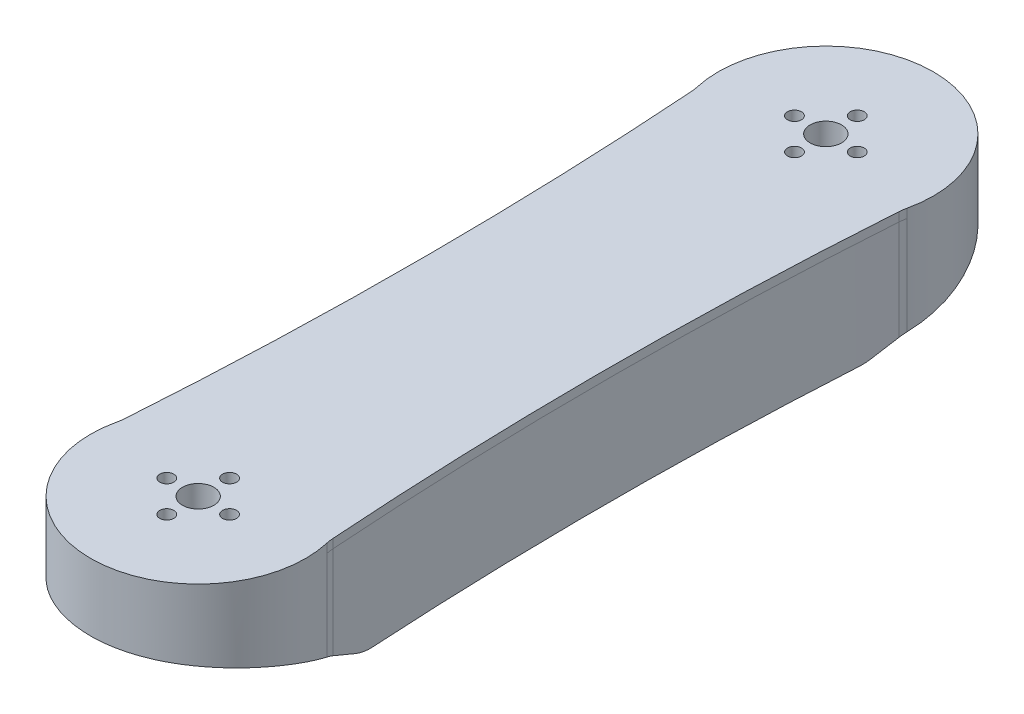
SolidWorks part; units mm, degrees
ref_plane "前视基准面" through (0, 0, 0) normal (0, 0, 1) x (1, 0, 0)
ref_plane "上视基准面" through (0, 0, 0) normal (0, 1, 0) x (1, 0, 0)
ref_plane "右视基准面" through (0, 0, 0) normal (1, 0, 0) x (0, 0, -1)
other "Configuration Table"
sketch "草图1" plane through (0, 0, 0) normal (0, 1, 0) x (1, 0, 0)
  line L0 (0, 140) -> (0, 0) construction
  line L1 (-23.2379, 6) -> (23.2379, 6) construction
  line L2 (-23.2379, 134) -> (23.2379, 134) construction
  circle A0 centre (0, 0) radius 24
  circle A1 centre (0, 140) radius 24
  spline S0 degree 2 poles (-23.2379, 134) (-18.7446, 70.0098) (-23.2379, 6) knots 0 0 0 1 1 1
  spline S1 degree 2 poles (23.2379, 134) (18.7446, 70.0098) (23.2379, 6) knots 0 0 0 1 1 1
  dimension "D1" = 48
  dimension "D2" = 140
  dimension "D3" = 6
  dimension "D4" = 6
  dimension "D5" = 60
  dimension "D6" = 42
extrude "凸台-拉伸1" add sketch "草图1" along normal blind 24 contours S1 A1 S0 A0 region at (0, 0, -69.9998)
extrude "凸台-拉伸2" add sketch "草图1<3>" along normal blind 26 contours A1 | A0 region at (0, 0, -140)
sketch "草图1<3>" plane through (0, 0, 0) normal (0, 1, 0) x (1, 0, 0) same geometry as "草图1"
sketch "草图2" plane through (0, 0, 0) normal (1, 0, 0) x (0, 0, -1)
  line L0 (-24, 0) -> (14, 0)
  line L1 (24, 0) -> (-24, 0) construction
  line L2 (164, 0) -> (116, 0) construction
  line L3 (164, 0) -> (164, 11)
  line L4 (164, 0) -> (164, 26) construction
  line L5 (-24, 0) -> (-24, 11)
  line L6 (-24, 26) -> (-24, 0) construction
  line L7 (126, 0) -> (164, 0)
  line L8 (70, -17.1118) -> (70, 61.7377) construction
  spline S0 degree 2 poles (-24, 11) (-3.7798, 9.1799) (14, 0) knots 0 0 0 1 1 1
  spline S1 degree 2 poles (164, 11) (145.3218, 4.4125) (126, 0) knots 0 0 0 1 1 1
  dimension "D1" = 11
  dimension "D2" = 38
  dimension "D3" = 11
  dimension "D4" = 38
extrude "切除-拉伸1" cut sketch "草图2" against normal through all both and the other way through all
ref_plane "基准面1" through (0, 20, 0) normal (0, 1, 0) x (1, 0, 0)
sketch "草图4" plane through (0, 20, 0) normal (0, 1, 0) x (1, 0, 0)
  arc A2 (-23.2379, 134) -> (23.2379, 134) centre (0, 140) ccw
  arc A3 (23.2379, 6) -> (-23.2379, 6) centre (0, 0) ccw
  arc A4 (-23.2379, 134) -> (23.2379, 134) centre (0, 140) ccw
  arc A5 (23.2379, 6) -> (-23.2379, 6) centre (0, 0) ccw
  parabola Q2 (23.2379, 6) -> (23.2379, 134) focus (476.7779, 71.0037) apex (20.9934, 72.0025)
  parabola Q3 (23.2379, 6) -> (23.2379, 134) focus (476.7779, 71.0037) apex (20.9934, 72.0025)
  parabola Q4 (-23.2379, 134) -> (-23.2379, 6) focus (-476.7779, 71.0037) apex (-20.9934, 72.0025)
  parabola Q5 (-23.2379, 134) -> (-23.2379, 6) focus (-476.7779, 71.0037) apex (-20.9934, 72.0025)
  dimension "D1" = 0
extrude "凸台-拉伸3" add sketch "草图4" along normal up to surface (6 mm away) up to face at (0, 26, -116)
sketch "草图6" plane through (0, 20, 0) normal (0, 1, 0) x (1, 0, 0)
  arc A2 (20.3332, 134.75) -> (-20.3332, 134.75) centre (0, 140) ccw
  circle A3 centre (0, 140) radius 21
  arc A5 (-20.3332, 5.25) -> (20.3332, 5.25) centre (0, 0) ccw
  circle A6 centre (0, 0) radius 21
  dimension "D1" = 3
  dimension "D2" = 3
extrude "切除-拉伸3" cut sketch "草图6" against normal blind 122
sketch "草图7" plane through (0, 20, 0) normal (0, -1, 0) x (1, 0, 0)
  line L0 (0, 7) -> (0, -7) construction
  line L1 (0, 0) -> (0, -140) construction
  line L2 (0, -70) -> (-49.7161, -70) construction
  circle A0 centre (0, 0) radius 3.5
  circle A1 centre (0, 7) radius 1.565
  circle A2 centre (0, -7) radius 1.565
  circle A3 centre (0, -133) radius 1.565
  circle A4 centre (0, -140) radius 3.5
  circle A5 centre (0, -147) radius 1.565
  circle A6 centre (7, 0) radius 1.565
  circle A7 centre (-7, 0) radius 1.565
  circle A8 centre (7, -140) radius 1.565
  circle A9 centre (-7, -140) radius 1.565
  point P24 (0, 0)
  point P25 (0, 0)
  dimension "D1" = 7
  dimension "D2" = 3.13
  dimension "D3" = 7
  dimension "D5" = 7
  dimension "D4" = 7
extrude "切除-拉伸4" cut sketch "草图7" against normal blind 19
sketch "草图8" plane through (0, 0, 0) normal (0, 0, 1) x (1, 0, 0)
  line L0 (-8, 10) -> (8, 10) construction
  line L1 (-8, 17) -> (8, 17)
  line L2 (-8, 3) -> (8, 3)
  arc A0 (-8, 17) -> (-8, 3) centre (-8, 10) ccw
  arc A1 (8, 3) -> (8, 17) centre (8, 10) ccw
  point P2 (0, 10)
  dimension "D3" = 7
  dimension "D1" = 10
  dimension "D2" = 16
extrude "切除-拉伸5" cut sketch "草图8" against normal up to next
sketch "草图9" plane through (0, 0, 0) normal (0, -1, 0) x (1, 0, 0)
  line L0 (0, 0) -> (0, -140) construction
  line L1 (0, -70) -> (73.2785, -70) construction
  line L2 (-8, -44) -> (8, -44)
  line L3 (-8, -25) -> (8, -25)
  line L4 (-11, -28) -> (-11, -36)
  line L5 (-8, -39) -> (8, -39)
  line L6 (11, -28) -> (11, -36)
  line L7 (-11, -47) -> (-11, -55)
  line L8 (-8, -58) -> (8, -58)
  line L9 (11, -47) -> (11, -55)
  line L10 (-8, -63) -> (8, -63)
  line L11 (-11, -66) -> (-11, -74)
  line L12 (-8, -77) -> (8, -77)
  line L13 (11, -66) -> (11, -74)
  line L14 (-8, -82) -> (8, -82)
  line L15 (-11, -85) -> (-11, -93)
  line L16 (-8, -96) -> (8, -96)
  line L17 (11, -85) -> (11, -93)
  line L18 (-8, -101) -> (8, -101)
  line L19 (-11, -104) -> (-11, -112)
  line L20 (-8, -115) -> (8, -115)
  line L21 (11, -104) -> (11, -112)
  arc A0 (8, -25) -> (11, -28) centre (8, -28) cw
  arc A1 (-11, -36) -> (-8, -39) centre (-8, -36) ccw
  arc A2 (8, -39) -> (11, -36) centre (8, -36) ccw
  arc A3 (-8, -25) -> (-11, -28) centre (-8, -28) ccw
  arc A4 (8, -44) -> (11, -47) centre (8, -47) cw
  arc A5 (-11, -55) -> (-8, -58) centre (-8, -55) ccw
  arc A6 (8, -58) -> (11, -55) centre (8, -55) ccw
  arc A7 (-8, -44) -> (-11, -47) centre (-8, -47) ccw
  arc A8 (8, -63) -> (11, -66) centre (8, -66) cw
  arc A9 (-11, -74) -> (-8, -77) centre (-8, -74) ccw
  arc A10 (8, -77) -> (11, -74) centre (8, -74) ccw
  arc A11 (-8, -63) -> (-11, -66) centre (-8, -66) ccw
  arc A12 (8, -82) -> (11, -85) centre (8, -85) cw
  arc A13 (-11, -93) -> (-8, -96) centre (-8, -93) ccw
  arc A14 (8, -96) -> (11, -93) centre (8, -93) ccw
  arc A15 (-8, -82) -> (-11, -85) centre (-8, -85) ccw
  arc A16 (8, -101) -> (11, -104) centre (8, -104) cw
  arc A17 (-11, -112) -> (-8, -115) centre (-8, -112) ccw
  arc A18 (8, -115) -> (11, -112) centre (8, -112) ccw
  arc A19 (-8, -101) -> (-11, -104) centre (-8, -104) ccw
  point P12 (11, -25)
  point P17 (11, -39)
  point P20 (-11, -25)
  dimension "D3" = 3
  dimension "D1" = 22
  dimension "D2" = 14
  dimension "D5" = 5
  dimension "D4" = 5
extrude "切除-拉伸6" cut sketch "草图9" against normal up to next
fillet "圆角2" radius 10 8 edges at (23.2379, 25, -134) (-23.2379, 25, -134) (23.2379, 25, -6) (-23.2379, 25, -6) (23.2379, 12.9636, -134) (-23.2379, 12.9636, -134) (23.2379, 13.8536, -6) (-23.2379, 13.8536, -6)
fillet "圆角3" radius 10 4 edges at (19.1819, 0, -126) (-19.1819, 0, -126) (-19.1819, 0, -14) (19.1819, 0, -14)
